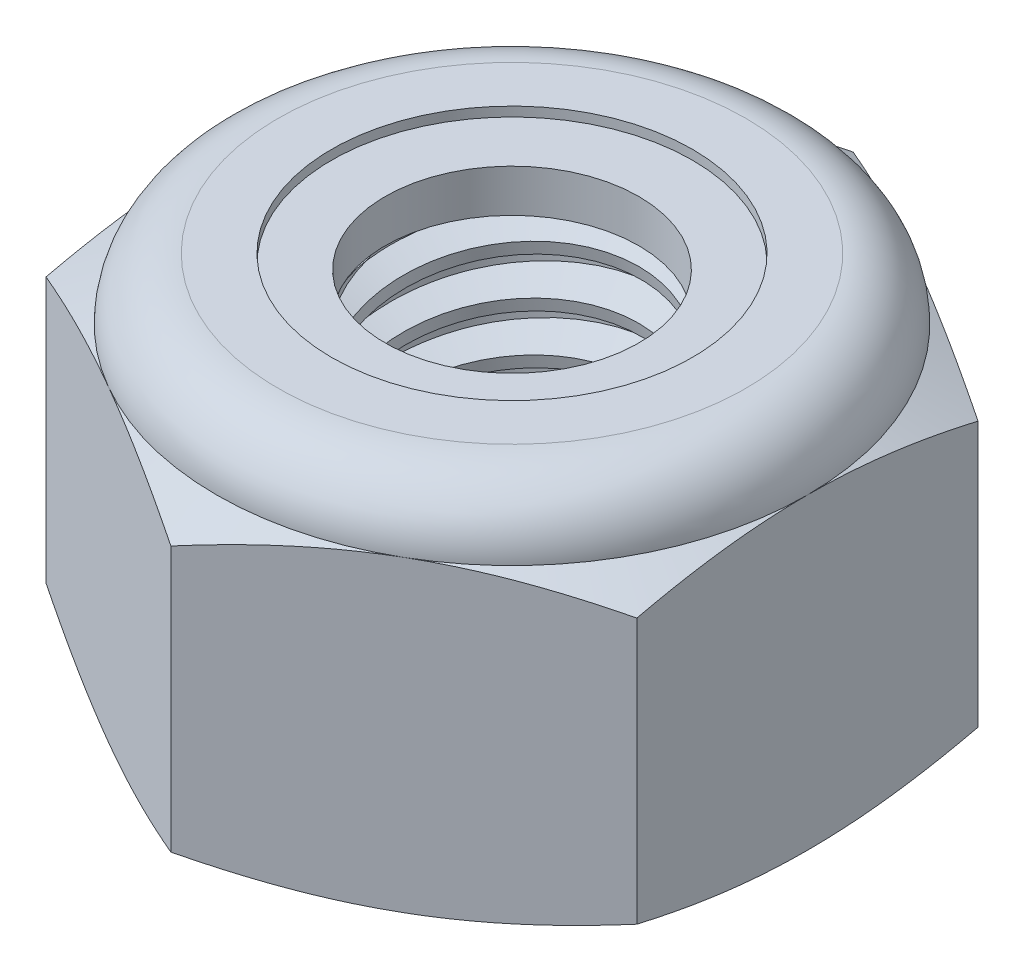
SolidWorks part; units mm, degrees
ref_plane "Front" through (0, 0, 0) normal (0, 0, 1) x (1, 0, 0)
ref_plane "Top" through (0, 0, 0) normal (0, 1, 0) x (1, 0, 0)
ref_plane "Right" through (0, 0, 0) normal (1, 0, 0) x (0, 0, -1)
sketch "Sketch1" plane through (0, 0, 0) normal (0, 1, 0) x (1, 0, 0)
  line L1 (0, 5.4993) -> (-4.7625, 2.7496)
  line L2 (-4.7625, 2.7496) -> (-4.7625, -2.7496)
  line L3 (-4.7625, -2.7496) -> (0, -5.4993)
  line L4 (0, -5.4993) -> (4.7625, -2.7496)
  line L5 (4.7625, -2.7496) -> (4.7625, 2.7496)
  line L6 (4.7625, 2.7496) -> (0, 5.4993)
  circle A0 centre (0, 0) radius 4.7625 construction
  dimension "Hex Flats" = 9.525
extrude "Extrude1" add sketch "Sketch1" along normal blind 5.9531
sketch "Sketch2" plane through (0, 0, 0) normal (1, 0, 0) x (0, 0, -1)
  line L0 (-2.413, 0) -> (-2.413, 5.9531) construction
  line L1 (0, 0) -> (2.413, 0)
  line L2 (0, 0) -> (0, 5.9531)
  line L3 (0, 5.9531) -> (2.413, 5.9531)
  line L4 (2.413, 0) -> (2.413, 5.9531)
  line L5 (-2.7496, 5.9531) -> (2.7496, 5.9531) construction
  line L7 (0, -2.413) -> (0, 0) construction
  dimension "Thread Dia" = 4.826
revolve "Revolve1" add sketch "Sketch2" angle 360 about L7
sketch "Sketch3" plane through (0, 0, 0) normal (1, 0, 0) x (0, 0, -1)
  line L0 (2.413, 5.9531) -> (-2.413, 5.9531) construction
  line L1 (-2.413, 5.9531) -> (-2.413, 5.1594) construction
  line L2 (-2.413, 5.1594) -> (2.413, 5.9531) construction
  line L3 (2.413, 5.9531) -> (2.4291, 5.8552) construction
  line L4 (2.4291, 5.8552) -> (2.5418, 5.1699)
  line L5 (2.5418, 5.1699) -> (2.0776, 5.3449)
  line L6 (2.0776, 5.3449) -> (2.0454, 5.5407)
  line L7 (2.0454, 5.5407) -> (2.4291, 5.8552)
  line L8 (2.0615, 5.4428) -> (2.4855, 5.5126) construction
  line L9 (2.413, 5.9531) -> (2.413, 5.5006) construction
  line L10 (2.413, 5.5006) -> (-2.413, 4.7069) construction
  line L11 (-2.413, 4.7069) -> (-2.413, 5.1594) construction
  line L12 (-0.1397, 5.9531) -> (0.1397, 4.2544) construction
  line L13 (-2.413, 0) -> (-2.413, 5.9531) construction
  line L14 (0, 5.9531) -> (2.413, 5.9531) construction
  line L15 (2.413, 0) -> (2.413, 5.9531) construction
  point P13 (0, 5.1038)
  dimension "D1" = 0.0992
  dimension "D2" = 0.1984
  dimension "Thread Pitch" = 0.7937
  dimension "D4" = 60
  dimension "D5" = 0.7937
revolve "Cut-Revolve1" cut sketch "Sketch3" angle 360 about L12
pattern_linear "LPattern1" count 8 spacing 0.7937 along (0, -1, 0) count 2 spacing 0.7937 along (0, 1, 0) of "Cut-Revolve1"
sketch "Sketch4" plane through (0, 0, 0) normal (1, 0, 0) x (0, 0, -1)
  line L0 (0, 5.9531) -> (2.413, 5.9531)
  line L1 (2.413, 5.9531) -> (2.0454, 5.7817)
  line L2 (2.0454, 5.7817) -> (2.0454, 0.1714)
  line L3 (2.0454, 0.1714) -> (2.413, 0)
  line L4 (2.413, 0) -> (0, 0)
  line L5 (0, 0) -> (0, 5.9531)
  line L6 (2.413, 0) -> (2.413, 5.9531) construction
  line L7 (0, 5.9531) -> (2.413, 5.9531) construction
  line L8 (0, 0) -> (2.413, 0) construction
  line L9 (0, 0) -> (0, 5.9531) construction
  line L10 (0, 5.9531) -> (0, 6.3587) construction
  dimension "D1" = 25
revolve "Cut-Revolve2" cut sketch "Sketch4" angle 360 about L10
combine bodies "Combine1" operation type subtract main body 112 bodies to subtract 111
sketch "Sketch5" plane through (0, 0, 0) normal (1, 0, 0) x (0, 0, -1)
  line L0 (0, 0) -> (4.7625, 0)
  line L1 (4.7625, 0) -> (5.4993, 0.3436)
  line L2 (5.4993, 0.3436) -> (5.4993, 4.6174)
  line L3 (5.4993, 4.6174) -> (4.7625, 4.9609)
  line L4 (3.7703, 5.9531) -> (3.7703, 7.2231)
  line L5 (3.7703, 7.2231) -> (6.7693, 7.2231)
  line L6 (6.7693, 7.2231) -> (6.7693, -1.27)
  line L7 (6.7693, -1.27) -> (0, -1.27)
  line L8 (0, -1.27) -> (0, 0)
  line L9 (4.7625, 4.9609) -> (4.7625, 0) construction
  line L10 (0, 0) -> (2.413, 0) construction
  line L13 (5.4993, 2.4805) -> (6.7693, 2.4805) construction
  line L14 (5.4993, 5.9531) -> (5.4993, 0) construction
  line L15 (0, 0) -> (0, 7.2231) construction
  line L20 (0, 7.2231) -> (3.7703, 7.2231) construction
  line L22 (0, 5.9531) -> (2.413, 5.9531) construction
  arc A0 (4.7625, 4.9609) -> (3.7703, 5.9531) centre (3.7703, 4.9609) ccw
  dimension "D1" = 25
  dimension "D2" = 1.27
  dimension "D3" = 5.9531
  dimension "D4" = 0.9922
revolve "Cut-Revolve3" cut sketch "Sketch5" angle 360 about L15
sketch "Sketch6" plane through (0, 0, 0) normal (1, 0, 0) x (0, 0, -1)
  line L0 (0, 4.9609) -> (4.6101, 4.9609)
  line L1 (3.7703, 5.8007) -> (2.9079, 5.8007)
  line L2 (0, 7.2231) -> (0, 4.9609)
  line L3 (2.9079, 7.2231) -> (0, 7.2231)
  line L4 (0, 7.2231) -> (3.7703, 7.2231) construction
  line L5 (0, 0) -> (0, 7.2231) construction
  line L6 (0, 7.2231) -> (0, 44.323) construction
  line L7 (2.9079, 5.8007) -> (2.9079, 7.2231)
  line L8 (3.7703, 5.9531) -> (3.7703, 5.8007) construction
  line L9 (2.9079, 5.8007) -> (2.0454, 5.8007) construction
  line L10 (2.0454, 5.8007) -> (2.0454, 5.7817) construction
  arc A0 (4.6101, 4.9609) -> (3.7703, 5.8007) centre (3.7703, 4.9609) ccw
  arc A1 (4.7625, 4.9609) -> (3.7703, 5.9531) centre (3.7703, 4.9609) ccw construction
  dimension "D1" = 0.1524
revolve "Cut-Revolve4" cut sketch "Sketch6" angle 360 about L6
sketch "Sketch7" plane through (0, 0, 0) normal (1, 0, 0) x (0, 0, -1)
  line L0 (2.0454, 5.0371) -> (4.5301, 5.0371)
  line L1 (3.7703, 5.7245) -> (2.0454, 5.7245)
  line L2 (2.0454, 5.7245) -> (2.0454, 5.0371)
  line L3 (2.0454, 5.0371) -> (0, 5.0371) construction
  line L4 (0, 5.0371) -> (0, 5.7245) construction
  line L5 (0, 5.7245) -> (2.0454, 5.7245) construction
  line L6 (2.0454, 5.0371) -> (2.0454, 4.9609) construction
  line L7 (0, 4.9609) -> (4.6101, 4.9609) construction
  line L8 (3.7703, 5.7245) -> (3.7703, 5.8007) construction
  arc A0 (4.5301, 5.0371) -> (3.7703, 5.7245) centre (3.7703, 4.9609) ccw
  arc A2 (4.6101, 4.9609) -> (3.7703, 5.8007) centre (3.7703, 4.9609) ccw construction
  dimension "D1" = 0.0762
revolve "Revolve2" add sketch "Sketch7" angle 360 about L4
equation "\"D1@Sketch3\"=\"Thread Pitch@Sketch3\"/8"
equation "\"D2@Sketch3\"=\"Thread Pitch@Sketch3\"/4"
equation "\"D5@Sketch3\"=\"Thread Pitch@Sketch3\""
equation "\"D4@LPattern1\"=\"Thread Pitch@Sketch3\""
equation "\"D3@LPattern1\"=\"Thread Pitch@Sketch3\""
equation "\"D1@LPattern1\"=\"Height@Extrude1\"/\"Thread Pitch@Sketch3\""
equation "\"D4@Sketch5\"=\"Height@Extrude1\"/6"
